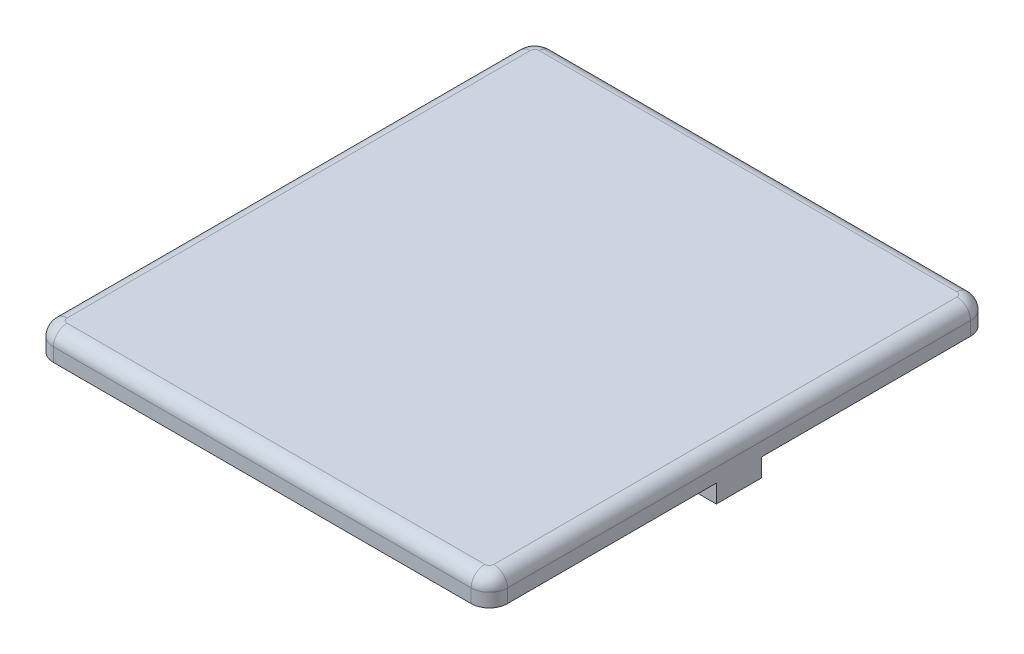
SolidWorks part; units mm, degrees
ref_plane "Front Plane" through (0, 0, 0) normal (0, 0, 1) x (1, 0, 0)
ref_plane "Top Plane" through (0, 0, 0) normal (0, 1, 0) x (1, 0, 0)
ref_plane "Right Plane" through (0, 0, 0) normal (1, 0, 0) x (0, 0, -1)
sketch "Sketch1" plane through (0, 0, 0) normal (0, 0, 1) x (1, 0, 0)
  line L1 (0, 0) -> (50, 0)
  line L2 (0, 0) -> (0, 3)
  line L3 (0, 3) -> (50, 3)
  line L4 (50, 0) -> (50, 3)
  dimension "D1" = 50
  dimension "D2" = 3
extrude "SolarPanet" add sketch "Sketch1" along normal mid plane 55
fillet "Fillet1" radius 2 4 edges at (0, 1.5, -27.5) (50, 1.5, -27.5) (50, 1.5, 27.5) (0, 1.5, 27.5)
fillet "Fillet2" radius 1.5 8 edges at (49.4142, 3, -26.9142) (50, 3, 0) (49.4142, 3, 26.9142) (25, 3, 27.5) (0.5858, 3, 26.9142) (0, 3, 0) (0.5858, 3, -26.9142) (25, 3, -27.5)
sketch "Sketch2" plane through (0, 0, 0) normal (0, -1, 0) x (1, 0, 0)
  line L0 (0, 25.5) -> (0, -25.5) construction
  line L1 (0, 2.5) -> (50, 2.5)
  line L2 (0, 2.5) -> (0, -2.5)
  line L3 (0, -2.5) -> (50, -2.5)
  line L4 (50, 2.5) -> (50, -2.5)
  line L5 (50, 25.5) -> (50, -25.5) construction
  line L6 (-10.9086, 0) -> (54.5975, 0) construction
  dimension "D1" = 5
  dimension "D2" = 2.5
extrude "BackSupport" add sketch "Sketch2" along normal blind 2
sketch "Sketch3" plane through (0, 0, 0) normal (0, -1, 0) x (1, 0, 0)
  line L0 (0, 25.5) -> (0, 2.5) construction
  circle A0 centre (25, 0) radius 6.5
  dimension "D1" = 13
  dimension "D2" = 25
extrude "SupportRing" add sketch "Sketch3" along normal blind 5 thin thin type one direction reverse wall 1.5
sketch "Sketch4" plane through (0, -5, 0) normal (0, -1, 0) x (1, 0, 0)
  circle A0 centre (25, 0) radius 5 construction
  circle A1 centre (25, 0) radius 5
extrude "Hole 4 Joystick" cut sketch "Sketch4" against normal up to surface (5 mm away) up to face at (25, 0, 15.1036)
sketch "Sketch5" plane through (0, 0, 0) normal (0, 0, 1) x (1, 0, 0)
  line L0 (25, 10.4384) -> (25, -15.8649) construction
  line L1 (18.5, -2) -> (18.5, -5) construction
  line L2 (25, -1.64) -> (30, -1.64)
  line L3 (25, -1.64) -> (25, -4.5)
  line L4 (25, -4.5) -> (30, -4.5)
  line L5 (18.5, -5) -> (31.5, -5) construction
  arc A0 (30, -1.64) -> (30, -4.5) centre (30, -3.07) cw
  dimension "D3" = 1.43
  dimension "D1" = 5
  dimension "D2" = 6.5
  dimension "D4" = 0.5
revolve "Round Cut 4 Joystick" cut sketch "Sketch5" angle 360 about L0
fillet "Fillet4" radius 0.5 2 edges at (25, -5, -6.5) (30, -5, 0)
equation "\"D2@Sketch2\"=\"D1@Sketch2\"/2"
equation "\"D2@Sketch3\"=25mm"
